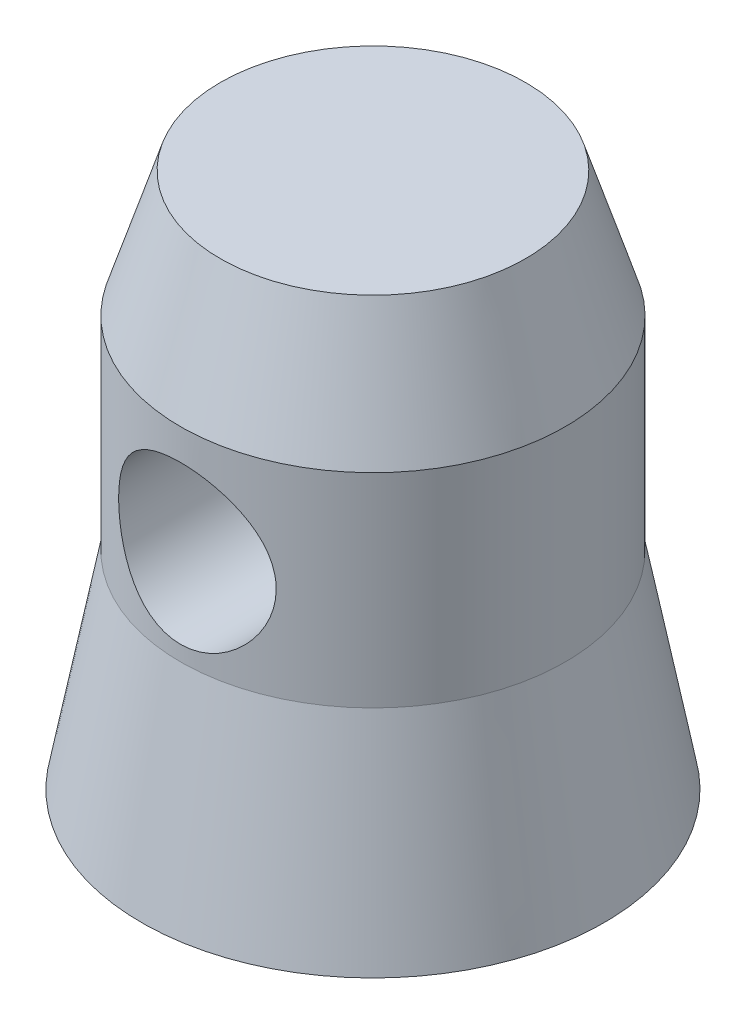
SolidWorks part; units mm, degrees
material "6061-T6 (SS)"
ref_plane "Front" through (0, 0, 0) normal (0, 0, 1) x (1, 0, 0)
ref_plane "Top" through (0, 0, 0) normal (0, 1, 0) x (1, 0, 0)
ref_plane "Right" through (0, 0, 0) normal (1, 0, 0) x (0, 0, -1)
sketch "Sketch1" plane through (0, 0, 0) normal (0, 0, 1) x (1, 0, 0)
  line L0 (0, 40.0685) -> (0, 3.31)
  line L1 (0, -50) -> (0, 50) construction
  line L2 (0, 40.0685) -> (11.4173, 40.0685)
  line L3 (11.4173, 40.0685) -> (14.3891, 30.672)
  line L4 (14.3891, 30.672) -> (14.3891, 15.432)
  line L5 (14.3891, 15.432) -> (17.2974, 0)
  line L6 (50, 0) -> (-50, 0) construction
  line L7 (10.5974, 0) -> (5, 3.31)
  line L8 (10.5974, 0) -> (17.2974, 0)
  line L9 (5, 3.31) -> (0, 3.31)
  dimension "D1" = 40.0685
  dimension "D2" = 6.7
  dimension "D3" = 3.31
  dimension "D4" = 11.4173
  dimension "D5" = 15.24
  dimension "D6" = 9.8552
  dimension "D7" = 5
  dimension "D8" = 17.2974
  dimension "D9" = 14.3891
revolve "Revolve1" add sketch "Sketch1" angle 360 about L0
sketch "Sketch2" plane through (0, 0, 0) normal (0, 0, 1) x (1, 0, 0)
  line L0 (0, 30.672) -> (0, 40.0685) construction
  line L1 (11.4173, 40.0685) -> (-11.4173, 40.0685) construction
  circle A0 centre (0, 22.4663) radius 5.8928
  dimension "D1" = 17.6022
  dimension "D2" = 11.7856
extrude "Cut-Extrude1" cut sketch "Sketch2" against normal through all and the other way through all
hole_wizard "M10x1.5 Tapped Hole1" positions "Sketch4" profile "Sketch5" tap size "M10x1.5" standard "ANSI Metric"
sketch "Sketch4" plane through (0, 3.31, 0) normal (0, -1, 0) x (-1, 0, 0)
  point P0 (0, 0)
sketch "Sketch5" plane through (0, 3.31, 0) normal (1, 0, 0) x (0, 0, -1)
  line L0 (0, 0) -> (0, 11.7993)
  line L1 (0, 11.7993) -> (4.25, 9.2456)
  line L2 (4.25, 9.2456) -> (4.25, 0)
  line L5 (4.25, 0) -> (0, 0)
  line L10 (0, 11.7993) -> (-4.25, 9.2456) construction
  line L11 (0, -6.35) -> (0, 107.95) construction
  dimension "Tap Drill Dia." = 8.5
  dimension "Tap Drill Depth" = 9.2456
  dimension "Drill Angle" = 118
cosmetic thread "Hole Thread1" parameters "D1"=7.2898, "D2"=10
